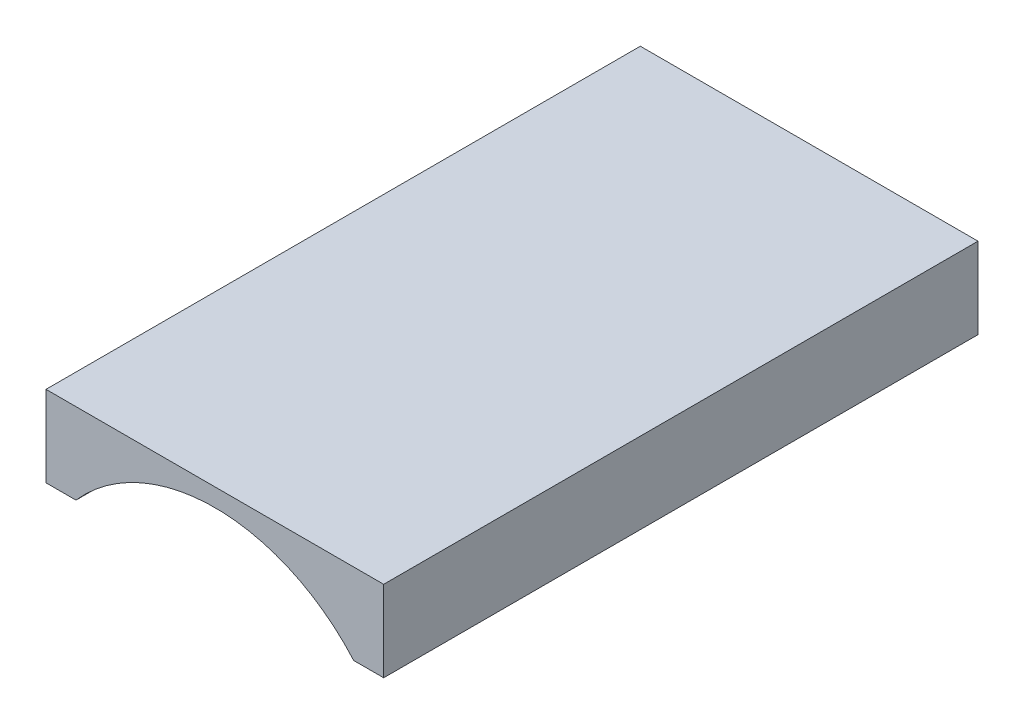
SolidWorks part; units mm, degrees
ref_plane "Front Plane" through (0, 0, 0) normal (0, 0, 1) x (1, 0, 0)
ref_plane "Top Plane" through (0, 0, 0) normal (0, 1, 0) x (1, 0, 0)
ref_plane "Right Plane" through (0, 0, 0) normal (1, 0, 0) x (0, 0, -1)
sketch "Sketch2" plane through (0, 0, 0) normal (0, 0, 1) x (1, 0, 0)
  line L0 (42.9348, 21.3088) -> (57.9348, 21.3088)
  line L1 (57.9348, 21.3088) -> (57.9348, 24.9061)
  line L2 (57.9348, 24.9061) -> (42.9348, 24.9061)
  line L3 (42.9348, 24.9061) -> (42.9348, 21.3088)
  dimension "D1" = 9
extrude "Boss-Extrude1" add sketch "Sketch2" against normal up to surface (26.4 mm away)
sketch "Sketch3" plane through (0, 0, 0) normal (0, 0, 1) x (1, 0, 0)
  line L0 (42.9348, 21.3088) -> (57.9348, 21.3088) construction
  line L1 (44.2663, 21.3088) -> (56.6032, 21.3088)
  arc A0 (56.6032, 21.3088) -> (44.2663, 21.3088) centre (50.4348, 15.9061) ccw
  dimension "D1" = 8.2
extrude "Cut-Extrude1" cut sketch "Sketch3" against normal up to surface (26.4 mm away) up to face at (50.4348, 23.1075, -26.4)
